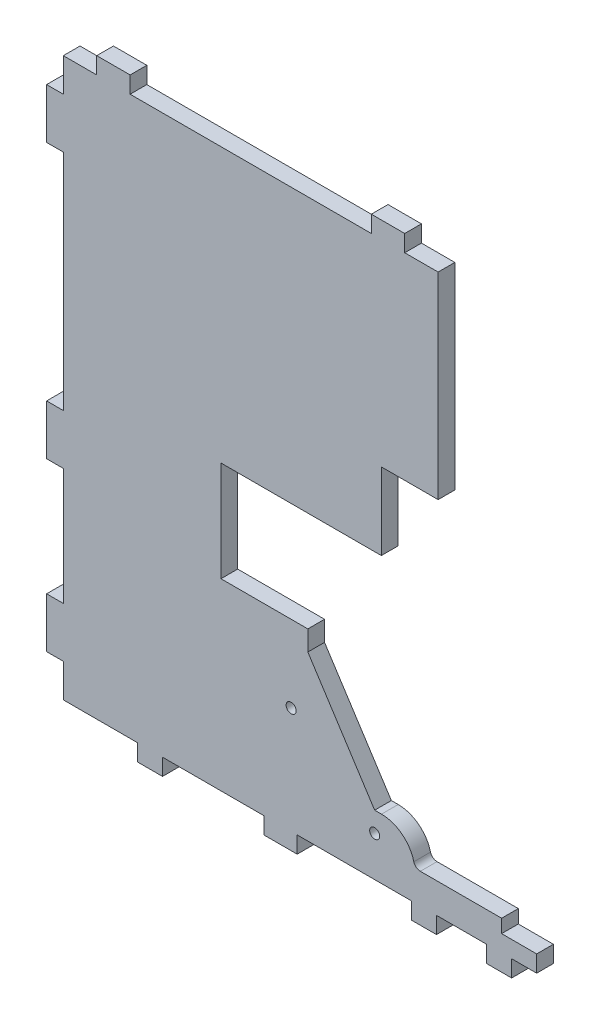
SolidWorks part; units mm, degrees
ref_plane "Plan de face" through (0, 0, 0) normal (0, 0, 1) x (1, 0, 0)
ref_plane "Plan de dessus" through (0, 0, 0) normal (0, 1, 0) x (1, 0, 0)
ref_plane "Plan de droite" through (0, 0, 0) normal (1, 0, 0) x (0, 0, -1)
sketch "Esquisse1" plane through (0, 0, 0) normal (0, 0, 1) x (1, 0, 0)
  line L0 (11, 49) -> (31, 18)
  line L1 (0, 0) -> (37, 0)
  line L2 (0, 0) -> (0, 55)
  line L3 (0, 55) -> (11, 55)
  line L4 (37, 0) -> (37, 18)
  line L6 (11, 55) -> (11, 49)
  line L7 (31, 18) -> (37, 18)
  circle A0 centre (6, 32) radius 1.5
  circle A1 centre (31, 12) radius 1.5
  dimension "D3" = 20
  dimension "D4" = 3
  dimension "D1" = 6
  dimension "D2" = 55
  dimension "D5" = 12
  dimension "D6" = 6
  dimension "D7" = 25
  dimension "D8" = 11
  dimension "D9" = 6
  dimension "D10" = 6
  dimension "D11" = 6
extrude "Boss.-Extru.1" add sketch "Esquisse1" along normal blind 5
sketch "Esquisse2" plane through (0, 0, 5) normal (0, 0, 1) x (1, 0, 0)
  line L0 (37, 18) -> (31, 18) construction
  line L1 (37, 0) -> (42, 0)
  line L2 (37, 0) -> (37, 18)
  line L3 (49.5, 0) -> (64.5, 0)
  line L4 (11, 55) -> (0, 55) construction
  line L5 (72, 0) -> (72, -5)
  line L6 (72, -5) -> (64.5, -5)
  line L7 (64.5, 0) -> (64.5, -5)
  line L8 (72, 0) -> (79.5, 0)
  line L9 (49.5, 0) -> (49.5, -5)
  line L10 (49.5, -5) -> (42, -5)
  line L11 (42, 0) -> (42, -5)
  line L13 (0, 0) -> (0, 55)
  line L14 (0, 55) -> (-15, 55)
  line L15 (40, 167) -> (50, 167)
  line L16 (0, 0) -> (-32.5, 0)
  line L17 (-40, 0) -> (-40, -5)
  line L18 (-15, 55) -> (-15, 85)
  line L19 (-40, -5) -> (-32.5, -5)
  line L20 (-62.19, 0) -> (-62.19, 10)
  line L21 (-62.19, 167) -> (-52.19, 167)
  line L22 (-32.5, 0) -> (-32.5, -5)
  line L23 (33, 85) -> (-15, 85)
  line L24 (50, 167) -> (50, 108)
  line L28 (-40, 0) -> (-62.19, 0)
  line L29 (-52.19, 167) -> (-52.19, 172)
  line L30 (-52.19, 172) -> (-42.19, 172)
  line L31 (-42.19, 167) -> (-42.19, 172)
  line L32 (-42.19, 167) -> (30, 167)
  line L33 (40, 167) -> (40, 172)
  line L34 (40, 172) -> (30, 172)
  line L35 (30, 167) -> (30, 172)
  line L36 (-62.19, 157) -> (-62.19, 167)
  line L37 (-62.19, 10) -> (-67.19, 10)
  line L38 (33, 85) -> (33, 108)
  line L39 (33, 108) -> (50, 108)
  line L40 (37, 18) -> (43, 18)
  line L41 (-62.19, 25) -> (-67.19, 25)
  line L42 (-67.19, 10) -> (-67.19, 25)
  line L43 (-62.19, 60) -> (-67.19, 60)
  line L44 (-62.19, 25) -> (-62.19, 60)
  line L45 (-62.19, 75) -> (-67.19, 75)
  line L46 (-67.19, 60) -> (-67.19, 75)
  line L47 (-62.19, 157) -> (-67.19, 157)
  line L48 (-62.19, 75) -> (-62.19, 142)
  line L49 (-62.19, 142) -> (-67.19, 142)
  line L50 (-67.19, 157) -> (-67.19, 142)
  line L51 (79.5, 0) -> (79.5, 5)
  line L52 (43, 18) -> (43, 9)
  line L53 (43, 9) -> (69, 9)
  line L56 (69, 9) -> (69, 5)
  line L57 (69, 5) -> (79.5, 5)
  circle A0 centre (31, 12) radius 1.5 construction
  dimension "D24" = 3
  dimension "D25" = 12
  dimension "D1" = 42.5
  dimension "D2" = 7.5
  dimension "D3" = 5
  dimension "D4" = 5
  dimension "D5" = 15
  dimension "D6" = 15
  dimension "D7" = 30
  dimension "D8" = 167
  dimension "D9" = 23
  dimension "D10" = 22.19
  dimension "D11" = 32.5
  dimension "D12" = 62.19
  dimension "D13" = 50
  dimension "D14" = 5
  dimension "D15" = 10
  dimension "D16" = 10
  dimension "D17" = 10
  dimension "D18" = 17
  dimension "D19" = 10
  dimension "D20" = 10
  dimension "D21" = 35
  dimension "D22" = 15
  dimension "D23" = 5
  dimension "D26" = 5
  dimension "D27" = 26
  dimension "D28" = 5
extrude "Boss.-Extru.2" add sketch "Esquisse2" against normal blind 5
fillet "Congé1" radius 10 1 edges at (43, 18, 2.5)
fillet "Congé2" radius 2 1 edges at (43, 9, 2.5)
sketch "Esquisse4" plane through (0, 0, 5) normal (0, 0, 1) x (1, 0, 0)
  line L0 (-32.5, 0) -> (42, 0) construction
  line L1 (-2.19, 0) -> (7.81, 0)
  line L2 (-2.19, 0) -> (-2.19, -5)
  line L3 (-2.19, -5) -> (7.81, -5)
  line L4 (7.81, 0) -> (7.81, -5)
  line L5 (-62.19, 10) -> (-62.19, 0) construction
  dimension "D1" = 10
  dimension "D2" = 5
  dimension "D3" = 60
extrude "Boss.-Extru.3" add sketch "Esquisse4" against normal blind 5
